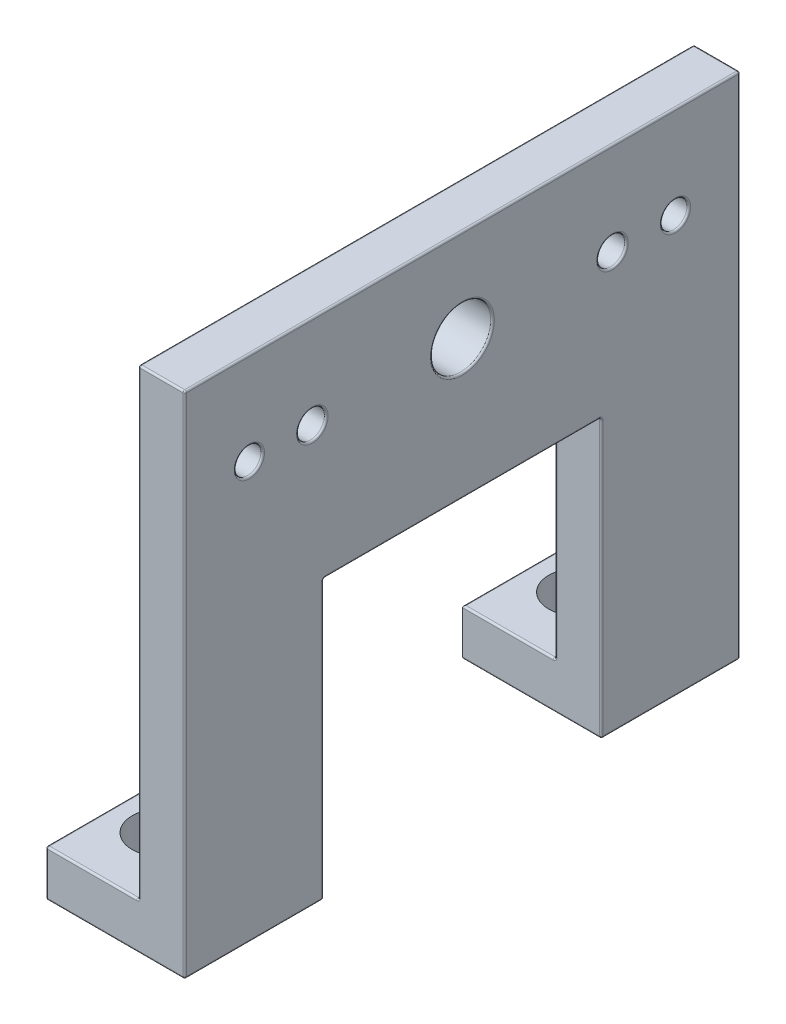
SolidWorks part; units mm, degrees
ref_plane "Front Plane" through (0, 0, 0) normal (0, 0, 1) x (1, 0, 0)
ref_plane "Top Plane" through (0, 0, 0) normal (0, 1, 0) x (1, 0, 0)
ref_plane "Right Plane" through (0, 0, 0) normal (1, 0, 0) x (0, 0, -1)
sketch "Sketch1" plane through (0, 0, 0) normal (0, 0, 1) x (1, 0, 0)
  line L1 (0, 0) -> (15, 0)
  line L2 (0, 0) -> (0, 5)
  line L3 (0, 5) -> (10, 5)
  line L6 (12.5, 0) -> (12.5, 55) construction
  line L7 (15, 55) -> (10, 55)
  line L8 (10, 5) -> (10, 55)
  line L10 (15, 5) -> (15, 55)
  line L11 (15, 5) -> (15, 0)
  dimension "D1" = 5
  dimension "D2" = 5
  dimension "D3" = 50
  dimension "D4" = 15
extrude "Boss-Extrude1" add sketch "Sketch1" along normal blind 60
sketch "Sketch2" plane through (15, 0, 0) normal (1, 0, 0) x (0, 0, -1)
  line L4 (0, 0) -> (0, 55)
  line L5 (0, 55) -> (-60, 55)
  line L6 (-60, 55) -> (-60, 0)
  line L7 (-60, 0) -> (0, 0)
  line L8 (0, 0) -> (0, 55) construction
  line L9 (0, 55) -> (-60, 55) construction
  line L10 (-60, 55) -> (-60, 0) construction
  line L12 (0, 0) -> (0, 55)
  line L13 (0, 55) -> (-60, 55)
  line L14 (-60, 55) -> (-60, 0)
  line L15 (-60, 0) -> (0, 0)
  line L20 (0, 0) -> (0, 55) construction
  line L21 (0, 55) -> (-60, 55) construction
  line L22 (-60, 55) -> (-60, 0) construction
  line L23 (-60, 0) -> (0, 0) construction
  circle A0 centre (-30, 45) radius 3.25
  circle A1 centre (-6.9875, 45) radius 1.435 construction
  circle A2 centre (-13.785, 45) radius 1.5 construction
  circle A3 centre (-46.215, 45) radius 1.5 construction
  circle A4 centre (-53.0125, 45) radius 1.435 construction
  circle A5 centre (-6.9875, 45) radius 1.435
  circle A6 centre (-13.785, 45) radius 1.5
  circle A7 centre (-46.215, 45) radius 1.5
  circle A8 centre (-53.0125, 45) radius 1.435
  point P2 (-30, 55)
  point P4 (-60, 27.5)
  point P6 (-30, 45)
  dimension "D4" = 6.5
  dimension "D2" = 0
  dimension "D3" = 10
  dimension "D1" = 0
extrude "Cut-Extrude1" cut sketch "Sketch2" against normal through all
sketch "Sketch3" plane through (0, 0, 0) normal (0, 0, -1) x (-1, 0, 0)
  line L0 (-15, 30) -> (-10, 30)
  line L6 (0, 0) -> (0, 5)
  line L7 (0, 5) -> (-10, 5)
  line L8 (-10, 5) -> (-10, 55)
  line L9 (-10, 55) -> (-15, 55)
  line L10 (-15, 55) -> (-15, 0)
  line L11 (-15, 0) -> (0, 0)
  line L12 (0, 0) -> (0, 5)
  line L13 (0, 5) -> (-10, 5)
  line L14 (-10, 5) -> (-10, 30)
  line L16 (-15, 30) -> (-15, 0)
  line L17 (-15, 0) -> (0, 0)
  dimension "D2" = 30
  dimension "D1" = 0
extrude "Cut-Extrude2" cut sketch "Sketch3" against normal blind 30 from offset 15 offset against normal yes
fillet "Fillet16" radius 0.2 44 edges at (5, 5, 15) (0, 5, 7.5) (0, 5, 52.5) (5, 5, 45) (12.5, 30, 45) (12.5, 30, 15) (0, 0, 52.5) (7.5, 0, 45) (0, 0, 7.5) (7.5, 0, 15) (5, 5, 60) (12.5, 55, 60) (7.5, 0, 60) (0, 2.5, 60) (7.5, 0, 0) (12.5, 55, 0) (5, 5, 0) (0, 2.5, 0) (15, 0, 52.5) (15, 27.5, 60) (15, 55, 30) (15, 27.5, 0) (15, 0, 7.5) (15, 15, 15) (15, 30, 30) (15, 15, 45) (15, 46.435, 53.0125) (15, 46.5, 46.215) (15, 46.5, 13.785) (15, 46.435, 6.9875) (15, 48.25, 30) (10, 30, 30) (10, 17.5, 15) (10, 5, 7.5) (10, 30, 0) (10, 55, 30) (10, 30, 60) (10, 5, 52.5) (10, 17.5, 45) (10, 46.435, 53.0125) (10, 46.5, 46.215) (10, 46.5, 13.785) (10, 46.435, 6.9875) (10, 48.25, 30)
sketch "Sketch4" plane through (0, 5, 0) normal (0, 1, 0) x (1, 0, 0)
  line L4 (0.2, -0.2) -> (0.2, -14.8)
  line L5 (0.2, -14.8) -> (9.8, -14.8)
  line L6 (9.8, -14.8) -> (9.8, -0.2)
  line L7 (9.8, -0.2) -> (0.2, -0.2)
  line L8 (0.2, -0.2) -> (0.2, -14.8) construction
  line L9 (0.2, -14.8) -> (9.8, -14.8) construction
  line L10 (9.8, -14.8) -> (9.8, -0.2) construction
  line L11 (9.8, -0.2) -> (0.2, -0.2) construction
  line L12 (9.8, -45.2) -> (0.2, -45.2)
  line L13 (0.2, -45.2) -> (0.2, -59.8)
  line L14 (0.2, -59.8) -> (9.8, -59.8)
  line L15 (9.8, -59.8) -> (9.8, -45.2)
  line L16 (9.8, -45.2) -> (0.2, -45.2) construction
  line L17 (0.2, -45.2) -> (0.2, -59.8) construction
  line L18 (0.2, -59.8) -> (9.8, -59.8) construction
  line L19 (9.8, -59.8) -> (9.8, -45.2) construction
  circle A0 centre (5, -7.5) radius 3.175
  circle A1 centre (5, -52.5) radius 3.175
  point P6 (9.8, -7.5)
  point P8 (5, -0.2)
  point P10 (9.8, -52.5)
  point P11 (5, -45.2)
  dimension "D3" = 6.35
  dimension "D1" = 0
  dimension "D2" = 0
extrude "Cut-Extrude3" cut sketch "Sketch4" against normal through all
